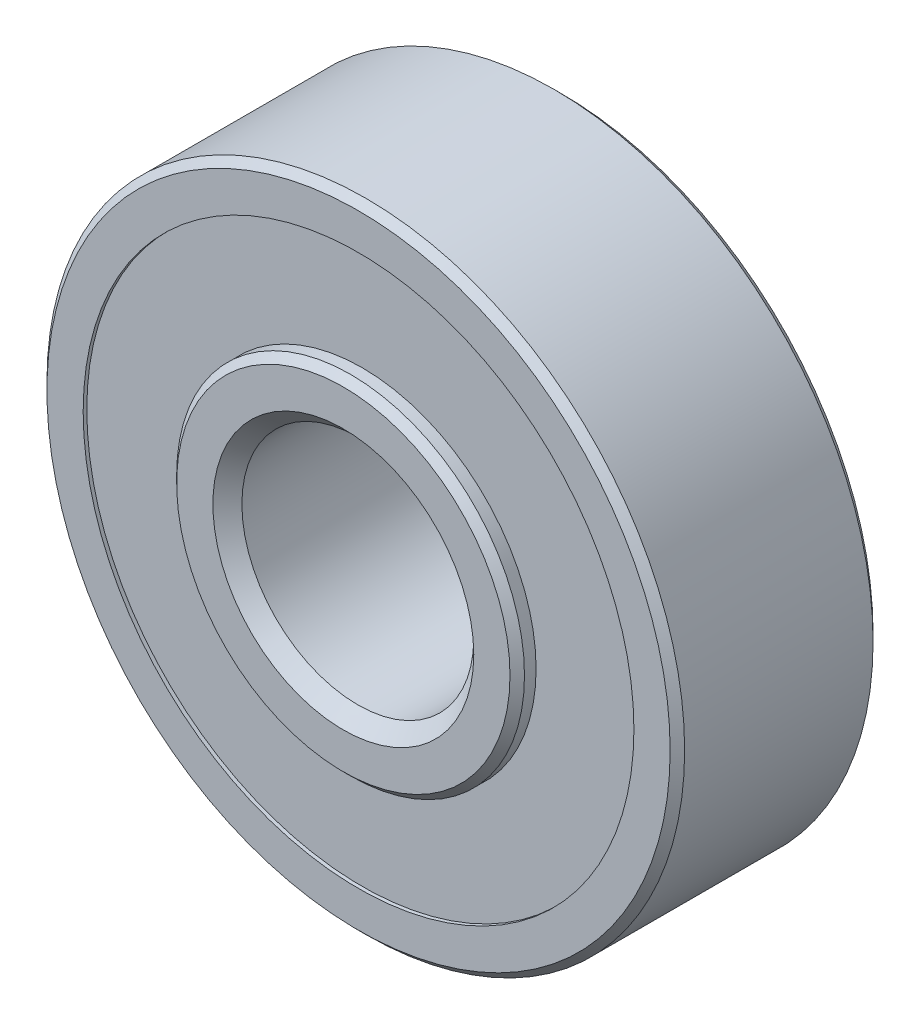
SolidWorks part; units mm, degrees
ref_plane "Front Plane" through (0, 0, 0) normal (0, 0, 1) x (1, 0, 0)
ref_plane "Top Plane" through (0, 0, 0) normal (0, 1, 0) x (1, 0, 0)
ref_plane "Right Plane" through (0, 0, 0) normal (1, 0, 0) x (0, 0, -1)
sketch "Sketch1" plane through (0, 0, 0) normal (0, 0, 1) x (1, 0, 0)
  circle A0 centre (0, 0) radius 11
  circle A1 centre (0, 0) radius 4
  circle A2 centre (0, 0) radius 9.5
  circle A3 centre (0, 0) radius 6
  point P7 (0, 0)
  dimension "D1" = 22
  dimension "D2" = 8
  dimension "D3" = 1.5
  dimension "D4" = 2
extrude "Boss-Extrude1" add sketch "Sketch1" along normal mid plane 7 contours A0 A2 region at (-10.6889, 0, 0)
extrude "Boss-Extrude2" add sketch "Sketch1<4>" along normal mid plane 8.05 separate body contours A3 A1 region at (-5.8303, 0, 0)
sketch "Sketch1<4>" plane through (0, 0, 0) normal (0, 0, 1) x (1, 0, 0) same geometry as "Sketch1"
extrude "Boss-Extrude3" add sketch "Sketch1<5>" along normal mid plane 6.75 contours A2 A3 region at (-9.2313, 0, 0)
sketch "Sketch1<5>" plane through (0, 0, 0) normal (0, 0, 1) x (1, 0, 0) same geometry as "Sketch1"
chamfer "Chamfer1" distance 0.5 angle 45 2 edges at (4, 0, -4.025) (4, 0, 4.025)
chamfer "Chamfer2" distance 0.25 angle 45 4 edges at (11, 0, -3.5) (11, 0, 3.5) (6, 0, 4.025) (6, 0, -4.025)
